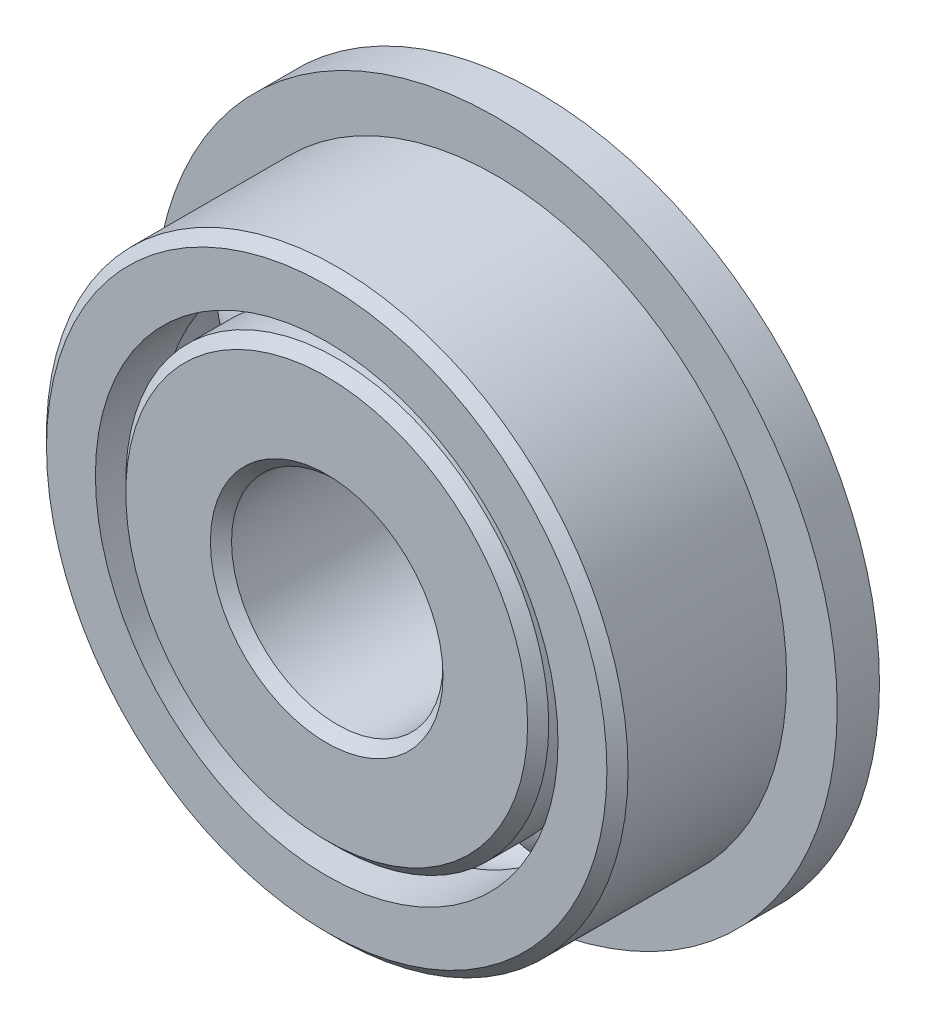
SolidWorks part; units mm, degrees
material "Plain Carbon Steel"
ref_plane "Front Plane" through (0, 0, 0) normal (0, 0, 1) x (1, 0, 0)
ref_plane "Top Plane" through (0, 0, 0) normal (0, 1, 0) x (1, 0, 0)
ref_plane "Right Plane" through (0, 0, 0) normal (1, 0, 0) x (0, 0, -1)
sketch "Sketch1" plane through (0, 0, 0) normal (1, 0, 0) x (0, 0, -1)
  line L0 (-3.175, 0) -> (3.175, 0) construction
  line L1 (0, 8.7312) -> (0, -8.7312) construction
  line L2 (2.8575, 8.7312) -> (-2.8575, 8.7312)
  line L3 (-2.8575, 8.7312) -> (-3.175, 8.4138)
  line L4 (-3.175, 8.4138) -> (-3.175, 6.9453)
  line L5 (-3.175, 6.9453) -> (-1.2392, 6.9453)
  line L6 (3.175, 6.9453) -> (1.2392, 6.9453)
  line L7 (3.175, 8.4138) -> (3.175, 6.9453)
  line L8 (2.8575, 8.7312) -> (3.175, 8.4138)
  line L9 (0, 8.7312) -> (0, 5.9531) construction
  line L10 (0, 5.9531) -> (0, 3.175) construction
  line L11 (3.175, 6.35) -> (3.175, -6.35) construction
  line L12 (-3.175, 3.175) -> (3.175, 3.175) construction
  line L13 (0, 4.3656) -> (0, 3.175) construction
  line L14 (0, 7.5406) -> (0, 8.7312) construction
  line L15 (3.175, 6.35) -> (0, 6.35) construction
  circle A1 centre (0, 5.9531) radius 1.5875 construction
  arc A2 (-1.2392, 6.9453) -> (1.2392, 6.9453) centre (0, 5.9531) cw
  point P14 (0, 3.175)
  point P22 (0, 4.3656)
  point P23 (0, 7.5406)
  dimension "D3" = 3.175
  dimension "Width" = 6.35
  dimension "OD" = 17.4625
  dimension "D1" = 45
  dimension "D2" = 0.3175
  dimension "D4" = 12.7
  dimension "D5" = 1.1906
  dimension "D6" = 0.5953
revolve "Revolve1" add sketch "Sketch1" angle 360 about L0
sketch "Sketch3" plane through (0, 0, 0) normal (1, 0, 0) x (0, 0, -1)
  line L1 (-3.175, 8.4138) -> (-3.175, 6.9453) construction
  line L2 (-2.8575, 8.7312) -> (-3.175, 8.4138) construction
  line L3 (-3.175, 4.9609) -> (-3.175, 3.4925) construction
  line L4 (-3.175, 3.4925) -> (-3.175, 6.0325)
  line L5 (-3.175, 3.4925) -> (-2.8575, 3.175)
  line L6 (-2.8575, 3.175) -> (4.4577, 3.175)
  line L7 (-3.175, 8.4138) -> (-3.175, -8.4138) construction
  line L8 (4.4577, 3.175) -> (4.7752, 3.4925)
  line L9 (0, 0) -> (4.7752, 0) construction
  line L13 (2.8575, 8.7312) -> (3.175, 8.4138) construction
  line L14 (-3.175, 6.0325) -> (-2.8575, 6.35)
  line L15 (-2.8575, 6.35) -> (-1.5371, 6.35)
  line L16 (1.5371, 6.35) -> (4.4577, 6.35)
  line L17 (4.4577, 6.35) -> (4.7752, 6.0325)
  line L18 (4.7752, 6.0325) -> (4.7752, 3.4925)
  circle A0 centre (0, 5.9531) radius 1.5875 construction
  arc A1 (-1.5371, 6.35) -> (1.5371, 6.35) centre (0, 5.9531) ccw
  dimension "D1" = 45
  dimension "Ring Wd" = 7.9502
  dimension "Inner Ring OD" = 12.7
revolve "Revolve3" add sketch "Sketch3" angle 360 about L0
sketch "Sketch6" plane through (0, 0, 0) normal (1, 0, 0) x (0, 0, -1)
  line L1 (3.175, 6.9453) -> (1.905, 6.9453)
  line L2 (3.175, 6.9453) -> (3.175, 10.2489)
  line L3 (3.175, 10.2489) -> (1.905, 10.2489)
  line L4 (1.905, 6.9453) -> (1.905, 10.2489)
  line L5 (3.175, 0) -> (-3.175, 0) construction
  dimension "Flange OD" = 20.4978
  dimension "Flange Thickness" = 1.27
revolve "Revolve6" add sketch "Sketch6" angle 360 about L5
sketch "Sketch4" plane through (0, 0, 0) normal (1, 0, 0) x (0, 0, -1)
  line L0 (-1.5875, 5.9531) -> (1.5875, 5.9531)
  circle A0 centre (0, 5.9531) radius 1.5875 construction
  arc A1 (1.5875, 5.9531) -> (-1.5875, 5.9531) centre (0, 5.9531) ccw
revolve "Revolve4" add sketch "Sketch4" angle 360 about L0
ref_axis "Axis1" through (0, 0, -3.175) along (0, 0, 1)
pattern_circular "CirPattern1" count 8 every 45 about axis through (0, 0, -3.175) along (0, 0, 1) of bodies 104
sketch "Sketch5" plane through (0, 0, 0) normal (1, 0, 0) x (0, 0, -1)
  line L0 (-3.175, 6.9453) -> (-1.2392, 6.9453) construction
  line L1 (-3.0162, 6.9453) -> (-1.5371, 6.9453)
  line L2 (-3.0162, 6.9453) -> (-3.0162, 6.35)
  line L3 (-3.0162, 6.35) -> (-1.5371, 6.35)
  line L4 (-1.5371, 6.9453) -> (-1.5371, 6.35)
  line L6 (3.175, 6.9453) -> (1.2392, 6.9453) construction
  line L7 (3.0163, 6.9453) -> (1.5371, 6.9453)
  line L8 (3.0163, 6.9453) -> (3.0163, 6.35)
  line L9 (3.0163, 6.35) -> (1.5371, 6.35)
  line L10 (1.5371, 6.9453) -> (1.5371, 6.35)
  line L12 (-2.8575, 8.7312) -> (-3.175, 8.4138) construction
  line L13 (3.175, 6.35) -> (0, 6.35) construction
  line L15 (-2.8575, 6.35) -> (-1.5371, 6.35) construction
  line L16 (3.0163, 6.9453) -> (3.0163, 8.5725) construction
  line L17 (2.8575, 8.7312) -> (3.175, 8.4138) construction
  point P18 (-3.0162, 8.5725)
revolve "Revolve5" [suppressed] add sketch "Sketch5" angle 360 about L0
equation "\"D2@Sketch1\" = \"Width@Sketch1\"*.05"
equation "\"D2@CirPattern1\" = 360/\"Balls@CirPattern1\""
equation "\"D4@Sketch1\"=\"Inner Ring OD@Sketch3\""
equation "\"D3@Sketch1\"=\"Width@Sketch1\"/2"
equation "\"D6@Sketch1\"=\"D5@Sketch1\"/2"
